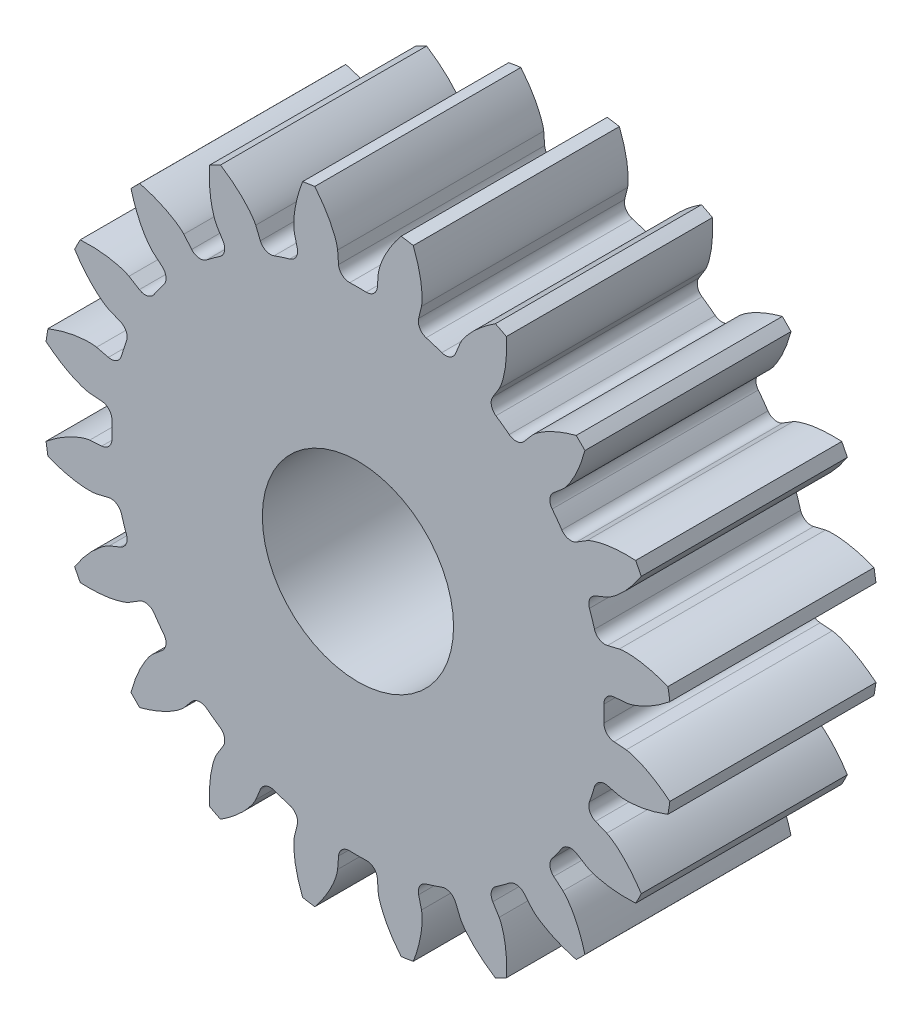
SolidWorks part; units mm, degrees
ref_plane "Front Plane" through (0, 0, 0) normal (0, 0, 1) x (1, 0, 0)
ref_plane "Top Plane" through (0, 0, 0) normal (0, 1, 0) x (1, 0, 0)
ref_plane "Right Plane" through (0, 0, 0) normal (1, 0, 0) x (0, 0, -1)
ref_axis "Gear Axis" through (0, 0, -0.4501) along (0, 0, 1)
sketch "Blank Sketch" plane through (0, 0, 0) normal (0, 0, 1) x (1, 0, 0)
  circle A0 centre (0, 0) radius 13.75
  dimension "OD" = 27.5
extrude "Blank" add sketch "Blank Sketch" along normal blind 9
sketch "Tooth Space Sketch" plane through (0, 0, 0) normal (0, 0, 1) x (1, 0, 0)
  line L0 (11.7126, 0.8876) -> (11.1829, 0.8474)
  line L1 (11.7126, -0.8876) -> (11.1829, -0.8474)
  line L2 (14.705, 2.9601) -> (14.705, -2.9601)
  arc A0 (11.1829, 0.8474) -> (10.744, 0.358) centre (11.2188, 0.3738) ccw
  arc A1 (10.744, -0.358) -> (11.1829, -0.8474) centre (11.2188, -0.3738) ccw
  arc A2 (10.744, -0.358) -> (10.744, 0.358) centre (0, 0) ccw
  spline S0 degree 4 poles (11.7126, 0.8876) (11.718, 0.8881) (11.7333, 0.8898) (11.7621, 0.8941) (11.8087, 0.9028) (11.8679, 0.9161) (11.9438, 0.936) (12.0325, 0.9629) (12.1291, 0.9959) (12.2333, 1.0356) (12.3362, 1.0785) (12.4379, 1.1244) (12.5383, 1.1729) (12.6587, 1.2348) (12.8015, 1.3135) (12.9658, 1.4118) (13.1489, 1.5308) (13.3319, 1.66) (13.5089, 1.7935) (13.6838, 1.9356) (13.8504, 2.0781) (14.0193, 2.2333) (14.173, 2.3803) (14.3404, 2.5526) (14.474, 2.694) (14.6449, 2.8885) (14.7442, 3.0057) (14.8584, 3.1456) (14.9081, 3.2092) (14.9387, 3.2482) knots 0 0 0 0 0 0.005377 0.015084 0.028532 0.04661 0.064855 0.092111 0.119476 0.146842 0.174209 0.201575 0.228941 0.256307 0.307035 0.361767 0.4165 0.471232 0.525964 0.580697 0.635429 0.690161 0.744894 0.799626 0.854358 0.909091 0.954545 1 1 1 1 1 construction
  spline S1 degree 4 poles (11.7126, 0.8876) (11.718, 0.8881) (11.7333, 0.8898) (11.7621, 0.8941) (11.8087, 0.9028) (11.8679, 0.9161) (11.9438, 0.936) (12.0325, 0.9629) (12.1291, 0.9959) (12.2333, 1.0356) (12.3362, 1.0785) (12.4379, 1.1244) (12.5383, 1.1729) (12.6587, 1.2348) (12.8015, 1.3135) (12.9658, 1.4118) (13.1489, 1.5308) (13.3319, 1.66) (13.5089, 1.7935) (13.6838, 1.9356) (13.8504, 2.0781) (14.0193, 2.2333) (14.173, 2.3803) (14.3404, 2.5526) (14.474, 2.694) (14.6078, 2.8463) (14.6723, 2.9214) (14.705, 2.9601) knots 0 0 0 0 0 0.005377 0.015084 0.028532 0.04661 0.064855 0.092111 0.119476 0.146842 0.174209 0.201575 0.228941 0.256307 0.307035 0.361767 0.4165 0.471232 0.525964 0.580697 0.635429 0.690161 0.744894 0.799626 0.854358 0.909091 0.909091 0.909091 0.909091 0.909091
  spline S2 degree 4 poles (11.7126, -0.8876) (11.718, -0.8881) (11.7333, -0.8898) (11.7621, -0.8941) (11.8087, -0.9028) (11.8679, -0.9161) (11.9438, -0.936) (12.0325, -0.9629) (12.1291, -0.9959) (12.2333, -1.0356) (12.3362, -1.0785) (12.4379, -1.1244) (12.5383, -1.1729) (12.6587, -1.2348) (12.8015, -1.3135) (12.9658, -1.4118) (13.1489, -1.5308) (13.3319, -1.66) (13.5089, -1.7935) (13.6838, -1.9356) (13.8504, -2.0781) (14.0193, -2.2333) (14.173, -2.3803) (14.3404, -2.5526) (14.474, -2.694) (14.6449, -2.8885) (14.7442, -3.0057) (14.8584, -3.1456) (14.9081, -3.2092) (14.9387, -3.2482) knots 0 0 0 0 0 0.005377 0.015084 0.028532 0.04661 0.064855 0.092111 0.119476 0.146842 0.174209 0.201575 0.228941 0.256307 0.307035 0.361767 0.4165 0.471232 0.525964 0.580697 0.635429 0.690161 0.744894 0.799626 0.854358 0.909091 0.954545 1 1 1 1 1 construction
  spline S3 degree 4 poles (11.7126, -0.8876) (11.718, -0.8881) (11.7333, -0.8898) (11.7621, -0.8941) (11.8087, -0.9028) (11.8679, -0.9161) (11.9438, -0.936) (12.0325, -0.9629) (12.1291, -0.9959) (12.2333, -1.0356) (12.3362, -1.0785) (12.4379, -1.1244) (12.5383, -1.1729) (12.6587, -1.2348) (12.8015, -1.3135) (12.9658, -1.4118) (13.1489, -1.5308) (13.3319, -1.66) (13.5089, -1.7935) (13.6838, -1.9356) (13.8504, -2.0781) (14.0193, -2.2333) (14.173, -2.3803) (14.3404, -2.5526) (14.474, -2.694) (14.6078, -2.8463) (14.6723, -2.9214) (14.705, -2.9601) knots 0 0 0 0 0 0.005377 0.015084 0.028532 0.04661 0.064855 0.092111 0.119476 0.146842 0.174209 0.201575 0.228941 0.256307 0.307035 0.361767 0.4165 0.471232 0.525964 0.580697 0.635429 0.690161 0.744894 0.799626 0.854358 0.909091 0.909091 0.909091 0.909091 0.909091
  dimension "Root" = 10.75
  dimension "Fillet" = 0.475
extrude "Tooth Space" cut sketch "Tooth Space Sketch" against normal through all both and the other way through all both
pattern_circular "Teeth" count 20 over 360 about axis through (0, 0, -0.4501) along (0, 0, 1) of "Tooth Space"
sketch "Bore Sketch" plane through (0, 0, 0) normal (0, 0, 1) x (1, 0, 0)
  circle A0 centre (0, 0) radius 4.175
  dimension "Bore" = 8.35
extrude "Bore" cut sketch "Bore Sketch" against normal through all both and the other way through all both
sketch "Sketch1" plane through (0, 0, 9) normal (0, 0, 1) x (1, 0, 0)
  circle A0 centre (0, 0) radius 4.175 construction
  circle A1 centre (0, 0) radius 4.175
  circle A2 centre (0, 0) radius 4 construction
  circle A3 centre (0, 0) radius 4
extrude "Boss-Extrude1" [suppressed] add sketch "Sketch1" against normal blind 50.25
equation "\"No. of Teeth\"= 20"
equation "\"Module\"= 1.25"
equation "\"Bore Diameter\" = 8.35"
equation "\"Pressure Angle\"= 20"
equation "\"Outer Diameter\"= ( \"No. of Teeth\" + 2 ) * \"Module\""
equation "\"Pitch Diameter\"= \"No. of Teeth\" * \"Module\""
equation "\"Backlash\" = IIF ( \"Module\" <= 1 , 0.3 * \"Module\" , 0.3 )"
equation "\"Arc Length\"= ( ( \"Module\" * pi ) / 2 + \"Backlash\" )"
equation "\"Fillet Radius\"= 0.38 * \"Module\""
equation "\"Tooth Depth\"= IIF ( \"Module\" <= 1.25 , \"Module\" * 2.4 , \"Module\" * 2.25 )"
equation "\"Face Width\"= 9"
equation "\"Root Diameter\"= \"Outer Diameter\" - 2 * \"Tooth Depth\""
equation "\"Base Diameter\"= \"Pitch Diameter\" * cos ( \"Pressure Angle\" )"
equation "\"Base Radius\"= \"Base Diameter\" / 2"
equation "\"Tooth Thickness\"= \"Module\" * pi - \"Arc Length\""
equation "\"Half Space Angle\"= ( \"Arc Length\" / \"Pitch Diameter\" ) * 180 / pi"
equation "\"Involute Fn\"= tan ( \"Pressure Angle\" ) - \"Pressure Angle\" * pi / 180"
equation "\"Flank Offset\"= \"Arc Length\" / \"Pitch Diameter\" - \"Involute Fn\""
equation "\"Tip Cap Diameter\"= \"Outer Diameter\" + 2 * \"Module\""
equation "\"Flank Start Diameter\"= IIF ( \"Base Diameter\" >= ( \"Root Diameter\" + 3 * \"Fillet Radius\" ) , \"Base Diameter\" , \"Root Diameter\" + 3 * \"Fillet Radius\" )"
equation "\"Involute t1\"= ( abs ( ( \"Flank Start Diameter\" / \"Base Diameter\" ) ^ 2 - 1 ) ) ^ 0.5"
equation "\"Involute t2\"= ( abs ( ( \"Tip Cap Diameter\" / \"Base Diameter\" ) ^ 2 - 1 ) ) ^ 0.5"
equation "\"Flank Arc Radius\"= ( \"Pitch Diameter\" / 2 ) * sin ( \"Pressure Angle\" )"
equation "\"Flank Centre Angle\"= \"Half Space Angle\" + \"Pressure Angle\""
equation "\"OD@Blank Sketch\"= \"Outer Diameter\""
equation "\"Width@Blank\"= \"Face Width\""
equation "\"Root@Tooth Space Sketch\"= \"Root Diameter\" / 2"
equation "\"Fillet@Tooth Space Sketch\"= \"Fillet Radius\""
equation "\"Count@Teeth\"= \"No. of Teeth\""
equation "\"Bore@Bore Sketch\"= \"Bore Diameter\""
